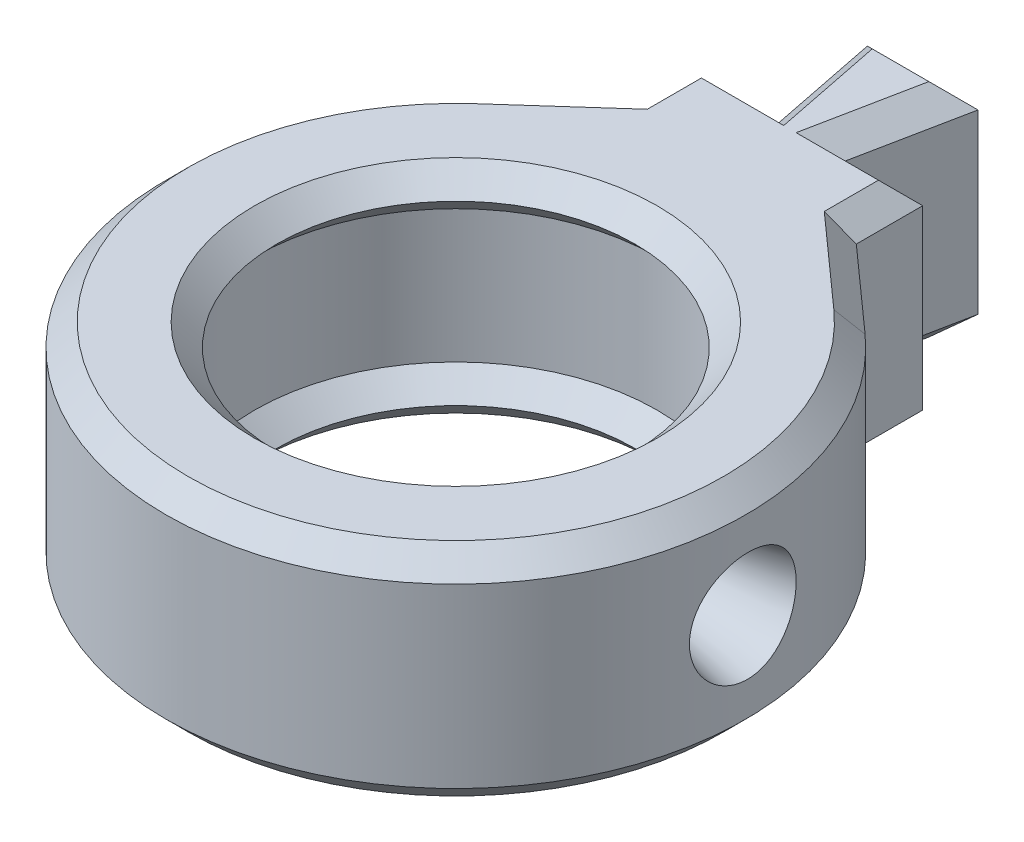
SolidWorks part; units mm, degrees
ref_plane "Front Plane" through (0, 0, 0) normal (0, 0, 1) x (1, 0, 0)
ref_plane "Top Plane" through (0, 0, 0) normal (0, 1, 0) x (1, 0, 0)
ref_plane "Right Plane" through (0, 0, 0) normal (1, 0, 0) x (0, 0, -1)
sketch "Sketch1" plane through (0, 0, 0) normal (0, 1, 0) x (1, 0, 0)
  line L0 (3.5, 0) -> (2.5, 5)
  line L1 (2.5, 5) -> (7.5, 5)
  line L2 (7.5, 5) -> (6.5, 0)
  line L3 (6.5, 0) -> (10, 0)
  line L4 (10, 0) -> (10, -3)
  line L5 (10, -3) -> (0, -3)
  line L6 (0, -3) -> (0, 0)
  line L7 (0, 0) -> (3.5, 0)
  line L8 (5, 5) -> (5, -3) construction
  line L9 (0, -3) -> (-3.7284, -6.3315)
  line L10 (10, -3) -> (13.7284, -6.3315)
  circle A0 centre (5, -16.1) radius 13.1
  circle A1 centre (5, -16.1) radius 8.1
  dimension "D8" = 16.2
  dimension "D1" = 10
  dimension "D2" = 5
  dimension "D3" = 5
  dimension "D4" = 3
  dimension "D5" = 3
  dimension "D6" = 1.5
  dimension "D7" = 5
extrude "Boss-Extrude1" add sketch "Sketch1" along normal blind 10 contours A0 A1 | A0 L10 L5 | L1 L8 L5 L4 L3 L2 | L8 L1 L0 L7 L6 L5 | A0 L5 L9 region at (3.0925, 0, -2.5185) region at (6.25, 0, -4.9057) region at (0.2602, 0, 3.6818) region at (9.7398, 0, 3.6818) region at (9.5392, 0, 4.2073)
sketch "Sketch2" plane through (0, 10, 0) normal (0, 1, 0) x (1, 0, 0)
  circle A0 centre (5, -16.1) radius 9.1
  circle A1 centre (5, -16.1) radius 8.1 construction
  dimension "D1" = 1
extrude "Cut-Extrude1" cut sketch "Sketch2" against normal blind 6 from offset 2 offset against normal yes
chamfer "Chamfer1" distance 1 angle 45 2 edges at (5, 8, 24.2) (5, 2, 24.2)
sketch "Sketch3" plane through (10, 0, 0) normal (1, 0, 0) x (0, 0, -1)
  line L0 (-6.3315, 10) -> (-29.2, 10) construction
  line L1 (5, 10) -> (5, 0) construction
  circle A0 centre (-16, 5) radius 2.5
  point P2 (0, 0)
  dimension "D1" = 5
  dimension "D2" = 5
  dimension "D3" = 21
extrude "Cut-Extrude2" cut sketch "Sketch3" against normal blind 6 draft 12 from offset 8.2
chamfer "Chamfer2" distance 1 angle 45 11 edges at (-1.8642, 10, 4.6657) (0, 10, 1.5) (1.75, 10, 0) (3, 10, -2.5) (5, 10, -5) (7, 10, -2.5) (8.25, 10, 0) (10, 10, 1.5) (11.8642, 10, 4.6657) (5, 10, 29.2) (5, 10, 24.2)
chamfer "Chamfer3" distance 1 angle 45 11 edges at (11.8642, 0, 4.6657) (10, 0, 1.5) (8.25, 0, 0) (7, 0, -2.5) (5, 0, -5) (3, 0, -2.5) (1.75, 0, 0) (0, 0, 1.5) (-1.8642, 0, 4.6657) (5, 0, 29.2) (5, 0, 24.2)
equation "\"D6@Sketch1\"=\"D4@Sketch1\"/2"
